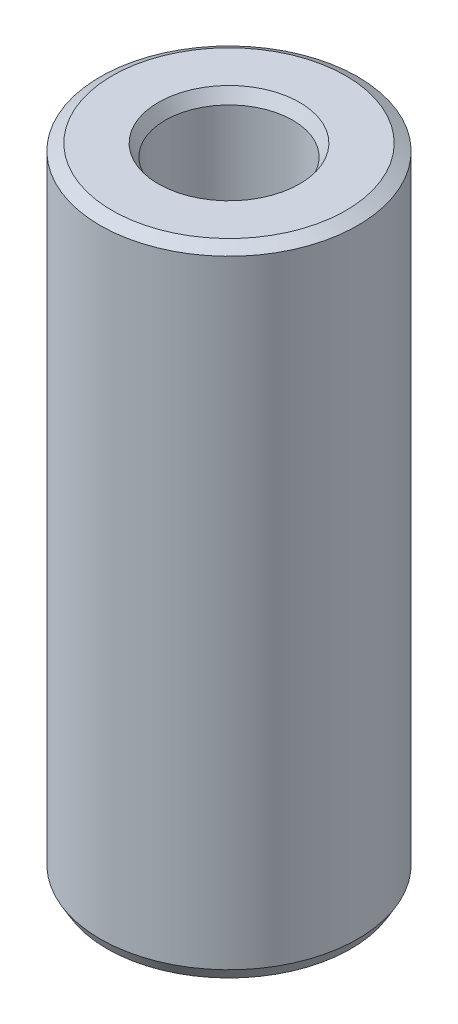
SolidWorks part; units mm, degrees
ref_plane "Front Plane" through (0, 0, 0) normal (0, 0, 1) x (1, 0, 0)
ref_plane "Top Plane" through (0, 0, 0) normal (0, 1, 0) x (1, 0, 0)
ref_plane "Right Plane" through (0, 0, 0) normal (1, 0, 0) x (0, 0, -1)
sketch "Sketch1" plane through (0, 0, 0) normal (0, 1, 0) x (1, 0, 0)
  circle A0 centre (0, 0) radius 27.5
  dimension "SLEEVE_OD" = 55
extrude "Boss-Extrude1" add sketch "Sketch1" along normal blind 135.9726
sketch "Sketch2" plane through (0, 0, 0) normal (0, 1, 0) x (1, 0, 0)
  circle A0 centre (0, 0) radius 13.6114
  dimension "BORE_D" = 27.2228
extrude "Cut-Extrude1" cut sketch "Sketch2" along normal through all
chamfer "Chamfer1" distance 1.4772 angle 60 4 edges at (0, 135.9726, 13.6114) (0, 0, 13.6114) (0, 0, 27.5) (0, 135.9726, 27.5) first distance on face at (0, 135.9726, 13.6114) first distance on face at (0, 0, 13.6114) first distance on face at (0, 135.9726, 27.5)
